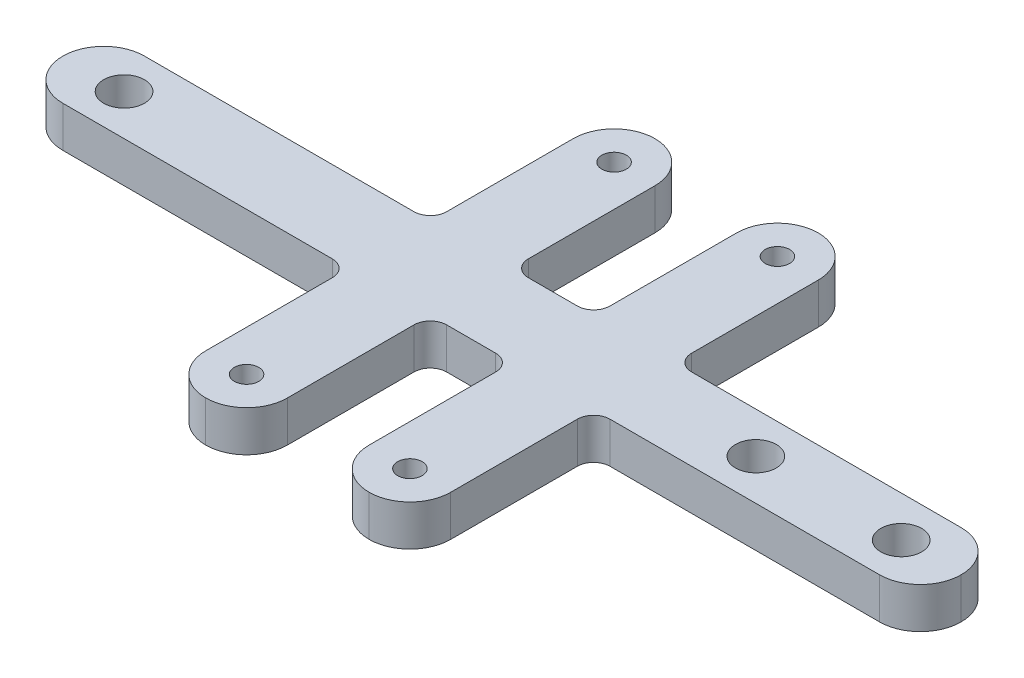
SolidWorks part; units mm, degrees
material "6061-T6 (SS)"
ref_plane "Front Plane" through (0, 0, 0) normal (0, 0, 1) x (1, 0, 0)
ref_plane "Top Plane" through (0, 0, 0) normal (0, 1, 0) x (1, 0, 0)
ref_plane "Right Plane" through (0, 0, 0) normal (1, 0, 0) x (0, 0, -1)
sketch "Sketch1" plane through (0, 0, 0) normal (0, 1, 0) x (1, 0, 0)
  line L1 (69.85, 6.35) -> (-69.85, 6.35)
  line L2 (69.85, 6.35) -> (69.85, -6.35)
  line L3 (69.85, -6.35) -> (-69.85, -6.35)
  line L4 (-69.85, 6.35) -> (-69.85, -6.35)
  line L5 (69.85, 6.35) -> (-69.85, -6.35) construction
  line L6 (69.85, -6.35) -> (-69.85, 6.35) construction
  point P0 (0, 0)
  dimension "D1" = 139.7
  dimension "D2" = 12.7
extrude "Boss-Extrude1" add sketch "Sketch1" along normal blind 6.35
sketch "Sketch2" plane through (0, 6.35, 0) normal (0, 1, 0) x (1, 0, 0)
  line L0 (-69.85, 0) -> (69.85, 0) construction
  line L1 (-69.85, 6.35) -> (-69.85, -6.35) construction
  line L2 (69.85, -6.35) -> (69.85, 6.35) construction
  circle A2 centre (-60.325, 0) radius 3.175
  circle A3 centre (37.9222, 0) radius 3.175
  circle A4 centre (60.5231, 0) radius 3.175
  dimension "D1" = 6.35
  dimension "D2" = 60.325
  dimension "D3" = 6.35
  dimension "D4" = 6.35
  dimension "D5" = 98.2472
  dimension "D6" = 22.6009
extrude "Cut-Extrude2" cut sketch "Sketch2" against normal blind 4.7625
sketch "Sketch3" plane through (0, 0, 0) normal (0, -1, 0) x (1, 0, 0)
  line L0 (69.85, 0) -> (-69.85, 0) construction
  line L1 (69.85, 6.35) -> (69.85, -6.35) construction
  line L2 (-69.85, -6.35) -> (-69.85, 6.35) construction
  circle A0 centre (-12.7, 0) radius 3.175
  circle A1 centre (12.7, 0) radius 3.175
  dimension "D1" = 6.35
  dimension "D2" = 6.35
  dimension "D3" = 12.7
  dimension "D4" = 12.7
extrude "Cut-Extrude3" cut sketch "Sketch3" against normal blind 4.7625
fillet "Fillet1" radius 6.35 4 edges at (69.85, 3.175, 6.35) (69.85, 3.175, -6.35) (-69.85, 3.175, 6.35) (-69.85, 3.175, -6.35)
hole_wizard "#6 Clearance Hole1" positions "Sketch5" profile "Sketch4" hole size "#6" standard "Ansi Inch"
sketch "Sketch5" plane through (0, 1.5875, 0) normal (0, 1, 0) x (-1, 0, 0)
  circle A0 centre (-60.5231, 0) radius 3.175 construction
  point P0 (-60.5231, 0)
  point P1 (-37.9222, 0)
  point P4 (60.325, 0)
sketch "Sketch4" plane through (60.5231, 1.5875, 0) normal (1, 0, 0) x (0, 0, 1)
  line L0 (0, 0) -> (0, 26.5408)
  line L1 (0, 26.5408) -> (1.8986, 25.4)
  line L2 (1.8986, 25.4) -> (1.8986, 0)
  line L5 (1.8986, 0) -> (0, 0)
  line L10 (0, 26.5408) -> (-1.8986, 25.4) construction
  line L11 (0, -6.35) -> (0, 107.95) construction
  dimension "Hole Dia." = 3.7973
  dimension "Hole Depth" = 25.4
  dimension "Drill Angle" = 118
hole_wizard "#6 Clearance Hole2" positions "Sketch7" profile "Sketch6" hole size "#6" standard "Ansi Inch"
sketch "Sketch7" plane through (0, 4.7625, 0) normal (0, -1, 0) x (1, 0, 0)
  circle A0 centre (-12.7, 0) radius 3.175 construction
  point P0 (-12.7, 0)
  point P1 (12.7, 0)
sketch "Sketch6" plane through (-12.7, 4.7625, 0) normal (1, 0, 0) x (0, 0, -1)
  line L0 (0, 0) -> (0, 26.5408)
  line L1 (0, 26.5408) -> (1.8986, 25.4)
  line L2 (1.8986, 25.4) -> (1.8986, 0)
  line L5 (1.8986, 0) -> (0, 0)
  line L10 (0, 26.5408) -> (-1.8986, 25.4) construction
  line L11 (0, -6.35) -> (0, 107.95) construction
  dimension "Hole Dia." = 3.7973
  dimension "Hole Depth" = 25.4
  dimension "Drill Angle" = 118
sketch "Sketch8" plane through (0, 6.35, 0) normal (0, 1, 0) x (1, 0, 0)
  line L1 (-6.35, 34.925) -> (-19.05, 34.925)
  line L2 (-6.35, 34.925) -> (-6.35, -34.925)
  line L3 (-6.35, -34.925) -> (-19.05, -34.925)
  line L4 (-19.05, 34.925) -> (-19.05, -34.925)
  line L5 (-6.35, 34.925) -> (-19.05, -34.925) construction
  line L6 (-6.35, -34.925) -> (-19.05, 34.925) construction
  line L7 (19.05, 34.925) -> (6.35, 34.925)
  line L8 (19.05, 34.925) -> (19.05, -34.925)
  line L9 (19.05, -34.925) -> (6.35, -34.925)
  line L10 (6.35, 34.925) -> (6.35, -34.925)
  line L11 (19.05, 34.925) -> (6.35, -34.925) construction
  line L12 (19.05, -34.925) -> (6.35, 34.925) construction
  point P0 (-12.7, 0)
  point P6 (12.7, 0)
  dimension "D1" = 12.7
  dimension "D2" = 12.7
  dimension "D3" = 69.85
  dimension "D4" = 69.85
extrude "Boss-Extrude2" add sketch "Sketch8" against normal blind 6.35
hole_wizard "#6 Clearance Hole3" positions "Sketch10" profile "Sketch9" hole size "#6" standard "Ansi Inch"
sketch "Sketch10" plane through (0, 6.35, 0) normal (0, 1, 0) x (-1, 0, 0)
  line L0 (12.7, -34.925) -> (12.7, 34.925) construction
  line L1 (6.35, -34.925) -> (19.05, -34.925) construction
  line L2 (19.05, 34.925) -> (6.35, 34.925) construction
  line L4 (-12.7, -34.925) -> (-12.7, 34.925) construction
  line L5 (-19.05, -34.925) -> (-6.35, -34.925) construction
  line L6 (-6.35, 34.925) -> (-19.05, 34.925) construction
  point P0 (12.7, -28.575)
  point P1 (12.7, 28.575)
  point P3 (-12.7, 28.575)
  point P5 (-12.7, -28.575)
  dimension "D1" = 6.35
  dimension "D2" = 6.35
  dimension "D3" = 6.35
  dimension "D4" = 6.35
sketch "Sketch9" plane through (-12.7, 6.35, -28.575) normal (1, 0, 0) x (0, 0, 1)
  line L0 (0, 0) -> (0, 26.5408)
  line L1 (0, 26.5408) -> (1.8986, 25.4)
  line L2 (1.8986, 25.4) -> (1.8986, 0)
  line L5 (1.8986, 0) -> (0, 0)
  line L10 (0, 26.5408) -> (-1.8986, 25.4) construction
  line L11 (0, -6.35) -> (0, 107.95) construction
  dimension "Hole Dia." = 3.7973
  dimension "Hole Depth" = 25.4
  dimension "Drill Angle" = 118
fillet "Fillet2" radius 2.54 8 edges at (19.05, 3.175, -6.35) (19.05, 3.175, 6.35) (6.35, 3.175, 6.35) (6.35, 3.175, -6.35) (-6.35, 3.175, -6.35) (-6.35, 3.175, 6.35) (-19.05, 3.175, 6.35) (-19.05, 3.175, -6.35)
fillet "Fillet3" radius 6.35 8 edges at (19.05, 3.175, -34.925) (6.35, 3.175, -34.925) (-6.35, 3.175, -34.925) (-19.05, 3.175, -34.925) (-19.05, 3.175, 34.925) (-6.35, 3.175, 34.925) (6.35, 3.175, 34.925) (19.05, 3.175, 34.925)
